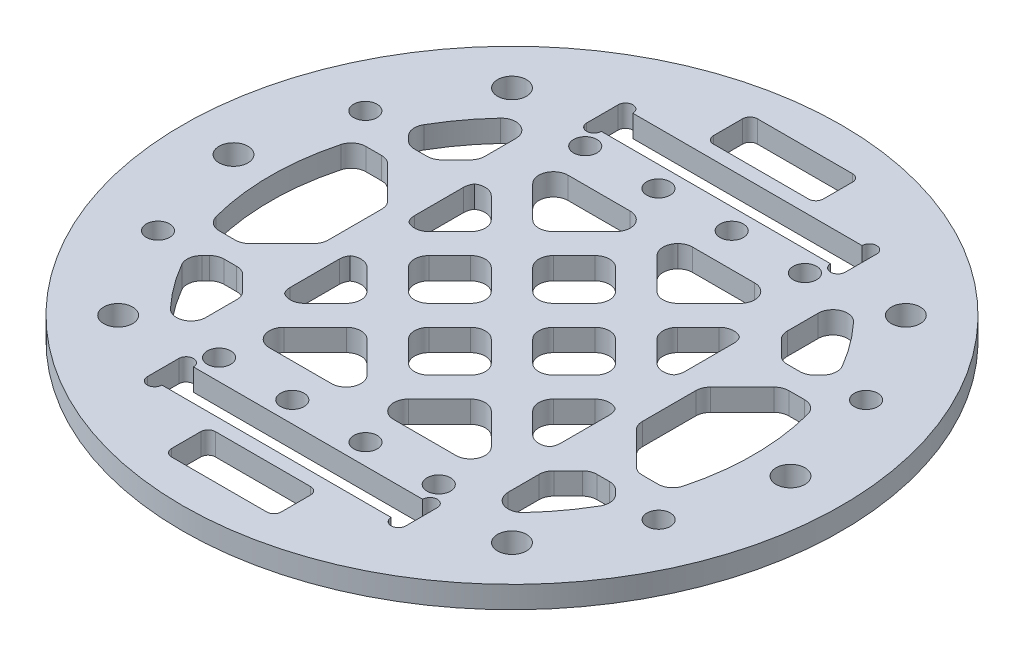
SolidWorks part; units mm, degrees
material "S-玻璃纤维"
ref_plane "前视基准面" through (0, 0, 0) normal (0, 0, 1) x (1, 0, 0)
ref_plane "上视基准面" through (0, 0, 0) normal (0, 1, 0) x (1, 0, 0)
ref_plane "右视基准面" through (0, 0, 0) normal (1, 0, 0) x (0, 0, -1)
other "Configuration Table"
sketch "草图1" plane through (0, 0, 0) normal (0, 1, 0) x (1, 0, 0)
  circle A0 centre (0, 0) radius 45
  dimension "D1" = 90
extrude "凸台-拉伸1" add sketch "草图1" along normal blind 3
sketch "草图2" plane through (0, 3, 0) normal (0, 1, 0) x (1, 0, 0)
  line L0 (-17.5, 32) -> (17.5, 32) construction
  line L1 (-17.5, 32) -> (-17.5, 28) construction
  line L2 (17.5, 32) -> (17.5, 28) construction
  line L3 (-17.5, 28) -> (17.5, 28) construction
  line L4 (-17.5, 32) -> (17.5, 28) construction
  line L5 (17.5, 32) -> (-17.5, 28) construction
  line L6 (0, 0) -> (50000, 0) construction
  line L7 (0, 0) -> (0, -50000) construction
  line L8 (17.5, -32) -> (17.5, -28) construction
  line L9 (-17.5, -28) -> (17.5, -28) construction
  line L10 (-17.5, -32) -> (-17.5, -28) construction
  line L11 (-17.5, -32) -> (17.5, -32) construction
  line L12 (-17.65, 32.15) -> (-17.65, 27.85)
  line L13 (-17.65, 27.85) -> (17.65, 27.85)
  line L14 (17.65, 32.15) -> (17.65, 27.85)
  line L15 (-17.65, 32.15) -> (17.65, 32.15)
  line L16 (-17.65, -32.15) -> (-17.65, -27.85)
  line L17 (-17.65, -27.85) -> (17.65, -27.85)
  line L18 (17.65, -32.15) -> (17.65, -27.85)
  line L19 (-17.65, -32.15) -> (17.65, -32.15)
  line L20 (-66.1976, 25) -> (49933.8024, 25) construction
  line L21 (-15, 25) -> (-5, 25) construction
  line L22 (-5, 25) -> (5, 25) construction
  line L23 (5, 25) -> (15, 25) construction
  circle A0 centre (-15, 25) radius 1.6
  circle A1 centre (-5, 25) radius 1.6
  circle A2 centre (5, 25) radius 1.6
  circle A3 centre (15, 25) radius 1.6
  circle A4 centre (15, -25) radius 1.6
  circle A5 centre (5, -25) radius 1.6
  circle A6 centre (-5, -25) radius 1.6
  circle A7 centre (-15, -25) radius 1.6
  point P1 (0, 30)
  dimension "D7" = 3.2
  dimension "D1" = 28
  dimension "D2" = 35
  dimension "D3" = 4
  dimension "D5" = 3
  dimension "D6" = 10
  dimension "D4" = 0.15
extrude "切除-拉伸1" cut sketch "草图2" against normal through all both and the other way through all
sketch "草图3" plane through (0, 3, 0) normal (0, 1, 0) x (1, 0, 0)
  line L0 (0, 0) -> (50000, 0) construction
  line L1 (0, 0) -> (0, 50000) construction
  line L2 (0, 0) -> (34.1835, 14.1593) construction
  circle A0 centre (34.1835, 14.1593) radius 1.6
  dimension "D2" = 3.2
  dimension "D1" = 37
  dimension "D3" = 22.5
extrude "切除-拉伸2" cut sketch "草图3" against normal through all both
pattern_circular "阵列(圆周)1" count 8 over 360 about axis through (0, 3, 0) along (0, -1, 0) skipping 1, 2, 5, 6 of "切除-拉伸2" reverse direction yes
sketch "草图5" plane through (0, 3, 0) normal (0, 1, 0) x (1, 0, 0)
  line L0 (0, 0) -> (50000, 0) construction
  line L1 (0, 0) -> (0, 50000) construction
  line L2 (38.025, 0) -> (0, 0) construction
  circle A0 centre (0, 0) radius 40 construction
  circle A1 centre (38.025, 0) radius 1.975
  dimension "D1" = 80
  dimension "D2" = 0
  dimension "D3" = 3.95
extrude "切除-拉伸3" cut sketch "草图5" against normal through all both
pattern_circular "阵列(圆周)2" count 8 over 360 about axis through (0, 3, 0) along (0, -1, 0) of "切除-拉伸3"
sketch "草图6" plane through (0, 3, 0) normal (0, 1, 0) x (1, 0, 0)
  line L0 (-17.65, 27.85) -> (17.65, 27.85) construction
  line L1 (17.65, 32.15) -> (-17.65, 32.15) construction
  line L2 (17.65, -27.85) -> (-17.65, -27.85) construction
  line L3 (-17.65, -32.15) -> (17.65, -32.15) construction
  line L4 (-17.65, -27.85) -> (-17.65, -32.15) construction
  line L5 (17.65, -32.15) -> (17.65, -27.85) construction
  line L6 (17.65, 27.85) -> (17.65, 32.15) construction
  circle A0 centre (-16.65, 27.85) radius 1
  circle A1 centre (-16.65, 32.15) radius 1
  circle A2 centre (16.65, 32.15) radius 1
  circle A3 centre (16.65, 27.85) radius 1
  circle A4 centre (16.65, -27.85) radius 1
  circle A5 centre (16.65, -32.15) radius 1
  circle A6 centre (-16.65, -27.85) radius 1
  circle A7 centre (-16.65, -32.15) radius 1
  point P31 (-16.65, 32.15)
  dimension "D1" = 2
extrude "切除-拉伸4" cut sketch "草图6" against normal through all both
ref_plane "基准面1" through (0, 0, -30) normal (0, 0, 1) x (1, 0, 0)
sketch "草图7" plane through (0, 3, 0) normal (0, 1, 0) x (1, 0, 0)
  line L4 (-15, 23.4) -> (15, 23.4) construction
  line L6 (0, 0) -> (0, -50000) construction
  line L7 (15, -23.4) -> (-15, -23.4) construction
  line L9 (-20.4, 20.4) -> (20.4, 20.4)
  line L10 (-20.65, -20.4) -> (20.65, -20.4)
  line L11 (-30.9063, -16.7642) -> (0, 14.1421)
  line L12 (-38.7848, 18.9858) -> (-29.799, 10)
  line L13 (0, 14.1421) -> (35.9563, -21.8142)
  line L14 (-2.0152, -21.8142) -> (21.4484, 1.6494)
  line L15 (-38.7848, -18.9858) -> (-29.799, -10)
  line L16 (20.65, 27.85) -> (20.65, 32.15)
  line L17 (20.65, 13) -> (20.65, 32.15)
  line L18 (-30.9063, 16.7642) -> (0, -14.1421)
  line L19 (20.65, -32.15) -> (20.65, -27.85)
  line L20 (20.65, -32.15) -> (20.65, -15.7474)
  line L21 (0, 19.799) -> (21.4484, -1.6494)
  line L22 (-20.65, -27.85) -> (-20.65, -32.15)
  line L23 (-20.65, -16.1196) -> (-20.65, -32.15)
  line L24 (21.4484, -10) -> (21.4484, 10)
  line L25 (-20.65, 32.15) -> (-20.65, 27.85)
  line L26 (-20.65, 32.15) -> (-20.65, 16.1196)
  line L27 (21.4484, -10) -> (31.4484, -10)
  line L28 (21.4484, 10) -> (31.4484, 10)
  line L29 (31.4484, -10) -> (31.4484, 10)
  line L30 (21.4484, -10) -> (31.4484, 10) construction
  line L31 (21.4484, 10) -> (31.4484, -10) construction
  line L32 (-21.4484, 10) -> (-31.4484, 10)
  line L33 (-31.4484, -10) -> (-31.4484, 10)
  line L34 (-21.4484, -10) -> (-31.4484, -10)
  line L35 (-21.4484, -10) -> (-21.4484, 10)
  line L36 (-18.4484, -13) -> (-18.4484, 13)
  line L37 (-18.4484, 13) -> (-34.4484, 13)
  line L38 (-34.4484, -13) -> (-34.4484, 13)
  line L39 (-18.4484, -13) -> (-34.4484, -13)
  line L40 (18.4484, -13) -> (18.4484, 13)
  line L41 (18.4484, 13) -> (34.4484, 13)
  line L42 (34.4484, -13) -> (34.4484, 13)
  line L43 (18.4484, -13) -> (34.4484, -13)
  line L44 (-20.4, -20.4) -> (20.4, 20.4) construction
  line L45 (-20.4, 20.4) -> (20.4, -20.4) construction
  line L46 (-3.4294, -20.4) -> (37.3706, 20.4)
  line L47 (-3.4294, 20.4) -> (37.3706, -20.4)
  line L48 (-20.4, -20.4) -> (20.4, 20.4) construction
  line L49 (-20.4, 20.4) -> (20.4, -20.4) construction
  line L50 (-37.3706, -20.4) -> (3.4294, 20.4)
  line L51 (-37.3706, 20.4) -> (3.4294, -20.4)
  line L52 (0, -14.1421) -> (35.9563, 21.8142)
  line L53 (-21.4484, 1.6494) -> (2.0152, -21.8142)
  line L54 (-38.7848, 18.9858) -> (2.0152, -21.8142) construction
  line L55 (-21.4484, -1.6494) -> (2.0152, 21.8142)
  line L56 (-38.7848, -18.9858) -> (2.0152, 21.8142) construction
  line L57 (-23.2284, 20.4) -> (17.5716, -20.4)
  line L58 (23.2284, 20.4) -> (-17.5716, -20.4)
  line L59 (-17.5716, 20.4) -> (23.2284, -20.4)
  line L60 (17.5716, 20.4) -> (-23.2284, -20.4)
  line L61 (-28.1907, 5.7504) -> (-16.9706, 16.9706) construction
  line L62 (1.6206, 15.35) -> (37.3706, -20.4) construction
  line L63 (3.0348, 16.7642) -> (38.7848, -18.9858) construction
  line L64 (0.2063, 13.9358) -> (35.9563, -21.8142) construction
  line L65 (-18.4484, 12.6643) -> (-15.5563, 15.5563)
  line L66 (-23.7696, 13) -> (-18.3848, 18.3848)
  line L67 (-29.6049, 7.1647) -> (-18.3848, 18.3848) construction
  line L68 (-26.7765, 4.3362) -> (-15.5563, 15.5563) construction
  line L69 (23.7696, 13) -> (18.3848, 18.3848)
  line L70 (18.4484, 12.6643) -> (15.5563, 15.5563)
  line L71 (-35.9563, -21.8142) -> (4.8437, 18.9858) construction
  line L72 (0, 0) -> (50000, 0) construction
  line L73 (23.7696, -13) -> (18.3848, -18.3848)
  line L74 (18.4484, -12.6643) -> (15.5563, -15.5563)
  line L75 (-18.4484, -12.6643) -> (-15.5563, -15.5563)
  line L76 (-23.7696, -13) -> (-18.3848, -18.3848)
  line L77 (29.799, 10) -> (38.7848, 18.9858)
  line L78 (-2.0152, -21.8142) -> (38.7848, 18.9858) construction
  line L79 (29.799, -10) -> (38.7848, -18.9858)
  line L80 (-35.9563, 21.8142) -> (4.8437, -18.9858) construction
  line L81 (-4.8437, -18.9858) -> (35.9563, 21.8142) construction
  circle A1 centre (-15, 25) radius 1.6 construction
  circle A2 centre (0, 0) radius 33
  circle A3 centre (0, 0) radius 33
  circle A4 centre (15, 25) radius 1.6 construction
  circle A5 centre (15, -25) radius 1.6 construction
  circle A6 centre (-15, -25) radius 1.6 construction
  point P16 (26.4484, 0)
  point P91 (0, 16.9706)
  dimension "D1" = 12
  dimension "D2" = 3
  dimension "D3" = 3
  dimension "D8" = 20
  dimension "D9" = 10
  dimension "D12" = 45
  dimension "D15" = 12
  dimension "D18" = 2
  dimension "D19" = 2
  dimension "D4" = 3
  dimension "D5" = 3
  dimension "D6" = 3
  dimension "D7" = 3
  dimension "D10" = 3
  dimension "D11" = 3
  dimension "D16" = 2
  dimension "D17" = 2
  dimension "D20" = 2
  dimension "D21" = 2
  dimension "D13" = 2
  dimension "D14" = 2
extrude "切除-拉伸5" cut sketch "草图7" against normal through all both contours L33 A3 | L34 L35 L32 L33 | L27 L29 L28 L24 | L29 A3 region at (-27.0167, 3, 0) region at (-32.0703, 3, 0) region at (27.0167, 3, 0) region at (32.0703, 3, 0)
extrude "切除-拉伸6" cut sketch "草图7<3>" against normal through all both contours L26 A3 L18 L37 L66 | L65 L36 L18 L55 L57 | L9 L59 L55 | L60 L13 L11 L59 | L60 L9 L21 | L40 L70 L58 L21 L52 | L52 A3 L17 L69 L41 | L60 L57 L11 L18 | L58 L59 L52 L13 | L74 L40 L13 L14 L59 | L57 L14 L10 | L57 L58 L18 L52 | L53 L58 L10 | L36 L75 L60 L53 L11 | L11 A3 L23 L76 L39 | L20 A3 L13 L43 L73 region at (-8.8511, 3, -17.2493) region at (-15.8932, 3, -8.4853) region at (8.8511, 3, -17.2493) region at (0, 3, -8.4853) region at (-8.4853, 3, 0) region at (-24.0854, 3, -18.0734) region at (8.4853, 3, 0) region at (15.8932, 3, -8.4853) region at (0, 3, 8.4853) region at (-15.8932, 3, 8.4853) region at (24.0854, 3, -18.0734) region at (15.8932, 3, 8.4853) region at (-8.8511, 3, 17.2493) region at (8.8511, 3, 17.2493) region at (-24.0854, 3, 18.0734) region at (24.0854, 3, 18.0734)
sketch "草图7<3>" plane through (0, 3, 0) normal (0, 1, 0) x (1, 0, 0) same geometry as "草图7"
fillet "圆角1" radius 2 84 edges at (-8.4853, 1.5, 5.6569) (-14.1421, 1.5, 0) (-8.4853, 1.5, -5.6569) (-2.8284, 1.5, 0) (-16.9706, 1.5, -14.1421) (-11.3137, 1.5, -8.4853) (-16.9706, 1.5, -2.8284) (-18.4484, 1.5, -4.3062) (-18.4484, 1.5, -12.6643) (0, 1.5, -2.8284) (-5.6569, 1.5, -8.4853) (0, 1.5, -14.1421) (5.6569, 1.5, -8.4853) (-17.5716, 1.5, 20.4) (-8.4853, 1.5, 11.3137) (-18.4484, 1.5, 4.3062) (-16.9706, 1.5, 2.8284) (-11.3137, 1.5, 8.4853) (-16.9706, 1.5, 14.1421) (-18.4484, 1.5, 12.6643) (16.9706, 1.5, 14.1421) (11.3137, 1.5, 8.4853) (16.9706, 1.5, 2.8284) (18.4484, 1.5, 4.3062) (18.4484, 1.5, 12.6643) (-20.65, 1.5, -16.1196) (-23.7696, 1.5, -13) (-27.1421, 1.5, -13) (-29.3084, 1.5, -15.1663) (-31.4484, 1.5, 10) (-31.4484, 1.5, -10) (31.4484, 1.5, -10) (31.4484, 1.5, 10) (17.5716, 1.5, 20.4) (8.4853, 1.5, 11.3137) (5.6569, 1.5, 8.4853) (0, 1.5, 14.1421) (-5.6569, 1.5, 8.4853) (0, 1.5, 2.8284) (20.65, 1.5, 16.1196) (23.7696, 1.5, 13) (27.1421, 1.5, 13) (29.3084, 1.5, 15.1663) (20.65, 1.5, 25.7406) (-27.1421, 1.5, 13) (-23.7696, 1.5, 13) (-20.65, 1.5, 16.1196) (-20.65, 1.5, 25.7406) (-29.3084, 1.5, 15.1663) (8.4853, 1.5, -11.3137) (17.5716, 1.5, -20.4) (-8.4853, 1.5, -11.3137) (-17.5716, 1.5, -20.4) (14.1421, 1.5, 0) (8.4853, 1.5, 5.6569) (2.8284, 1.5, 0) (8.4853, 1.5, -5.6569) (23.7696, 1.5, -13) (20.65, 1.5, -16.1196) (20.65, 1.5, -25.7406) (29.3084, 1.5, -15.1663) (27.1421, 1.5, -13) (16.9706, 1.5, -2.8284) (11.3137, 1.5, -8.4853) (16.9706, 1.5, -14.1421) (18.4484, 1.5, -12.6643) (18.4484, 1.5, -4.3062) (-20.65, 1.5, -25.7406) (1.4142, 1.5, 18.3848) (3.4294, 1.5, 20.4) (-1.4142, 1.5, 18.3848) (-3.4294, 1.5, 20.4) (-26.9706, 1.5, -10) (-21.4484, 1.5, 4.4778) (-26.9706, 1.5, 10) (-21.4484, 1.5, -4.4778) (26.9706, 1.5, -10) (26.9706, 1.5, 10) (21.4484, 1.5, 4.4778) (21.4484, 1.5, -4.4778) (3.4294, 1.5, -20.4) (1.4142, 1.5, -18.3848) (-3.4294, 1.5, -20.4) (-1.4142, 1.5, -18.3848)
sketch "草图8" plane through (0, 3, 0) normal (0, 1, 0) x (1, 0, 0)
  line L0 (-7.5, 34) -> (-7.5, 40)
  line L1 (-7.5, 34) -> (7.5, 34)
  line L2 (-7.5, 40) -> (7.5, 40)
  line L3 (7.5, 34) -> (7.5, 40)
  line L4 (-7.5, 34) -> (7.5, 40) construction
  line L5 (-7.5, 40) -> (7.5, 34) construction
  line L6 (0, 0) -> (50000, 0) construction
  line L7 (0, 0) -> (0, 50000) construction
  line L8 (-7.5, -40) -> (7.5, -40)
  line L9 (7.5, -34) -> (7.5, -40)
  line L10 (-7.5, -34) -> (7.5, -34)
  line L11 (-7.5, -34) -> (-7.5, -40)
  circle A0 centre (0, 38.025) radius 1.975 construction
  point P1 (0, 37)
  point P11 (0, 0)
  point P12 (0, 36.9173)
  point P15 (0, 37.2233)
  dimension "D1" = 6
  dimension "D2" = 15
extrude "切除-拉伸7" cut sketch "草图8" against normal through all both and the other way through all
fillet "圆角2" radius 1 8 edges at (7.5, 1.5, 34) (7.5, 1.5, 40) (-7.5, 1.5, 40) (-7.5, 1.5, 34) (7.5, 1.5, -40) (7.5, 1.5, -34) (-7.5, 1.5, -34) (-7.5, 1.5, -40)
